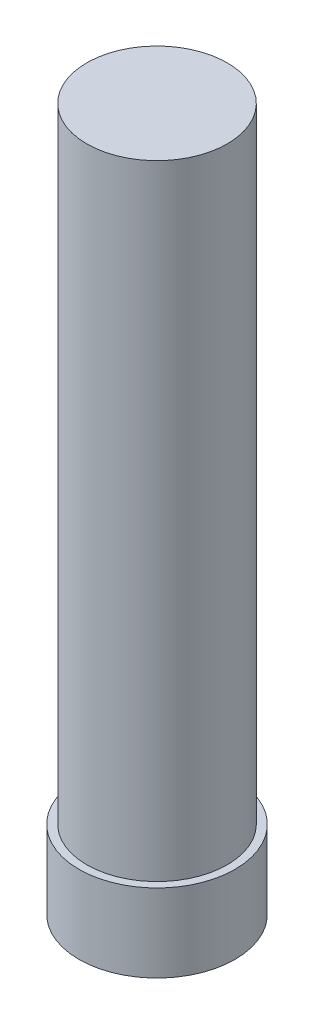
SolidWorks part; units mm, degrees
ref_plane "Front Plane" through (0, 0, 0) normal (0, 0, 1) x (1, 0, 0)
ref_plane "Top Plane" through (0, 0, 0) normal (0, 1, 0) x (1, 0, 0)
ref_plane "Right Plane" through (0, 0, 0) normal (1, 0, 0) x (0, 0, -1)
sketch "Sketch1" plane through (0, 0, 0) normal (0, 1, 0) x (1, 0, 0)
  circle A0 centre (0, 0) radius 12.7
  circle A1 centre (0, 0) radius 11.43
  dimension "D1" = 22.86
  dimension "D2" = 25.4
extrude "Boss-Extrude1" add sketch "Sketch1" along normal blind 101.6 contours A1 region at (0, 0, 0)
extrude "Boss-Extrude2" add sketch "Sketch1<3>" against normal blind 12.7 contours A0
sketch "Sketch1<3>" plane through (0, 0, 0) normal (0, 1, 0) x (1, 0, 0) same geometry as "Sketch1"
